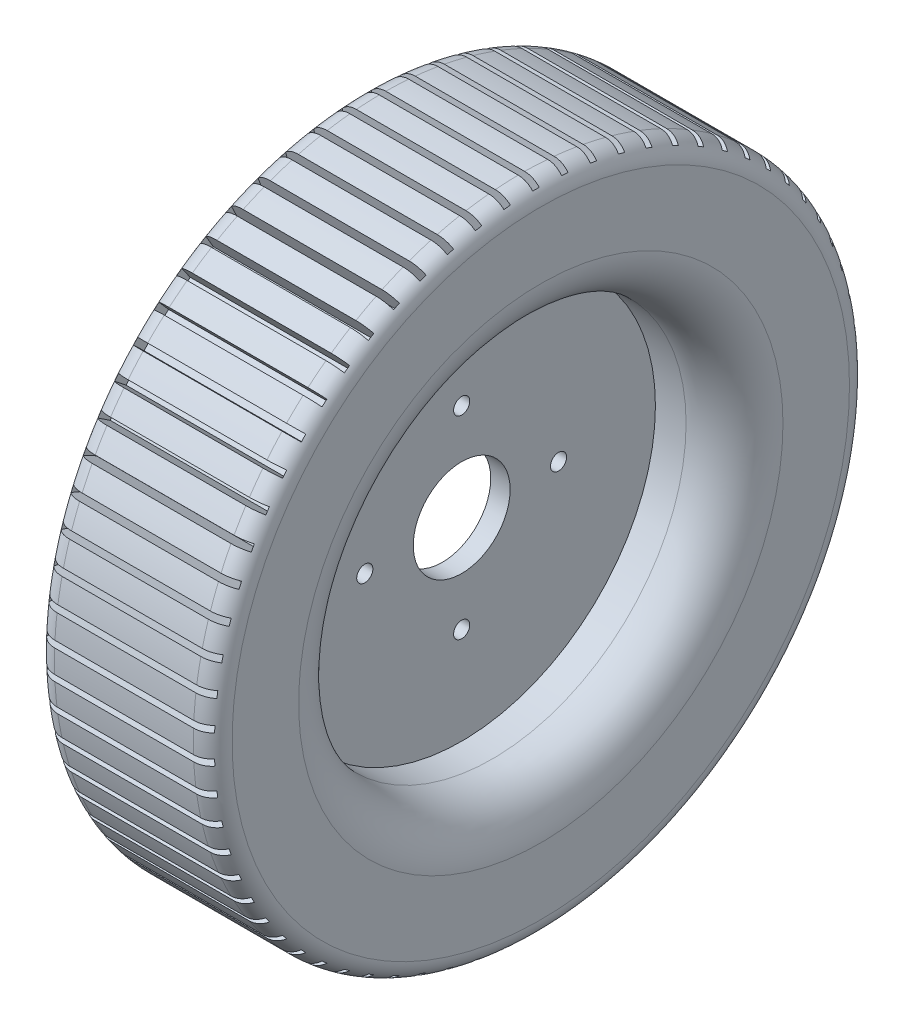
SolidWorks part; units mm, degrees
material "Rubber"
ref_plane "Front Plane" through (0, 0, 0) normal (0, 0, 1) x (1, 0, 0)
ref_plane "Top Plane" through (0, 0, 0) normal (0, 1, 0) x (1, 0, 0)
ref_plane "Right Plane" through (0, 0, 0) normal (1, 0, 0) x (0, 0, -1)
sketch "Sketch1" plane through (0, 0, 0) normal (1, 0, 0) x (0, 0, -1)
  circle A0 centre (0, 0) radius 101.6
  dimension "D1" = 203.2
extrude "Boss-Extrude1" add sketch "Sketch1" along normal mid plane 55
sketch "Sketch2" plane through (0, 0, 0) normal (1, 0, 0) x (0, 0, -1)
  circle A0 centre (0, 0) radius 60
  dimension "D1" = 120
extrude "Cut-Extrude1" cut sketch "Sketch2" against normal blind 500 from offset 3 offset against normal yes
extrude "Cut-Extrude2" cut sketch "Sketch2<2>" along normal blind 500 from offset 3
sketch "Sketch2<2>" plane through (0, 0, 0) normal (1, 0, 0) x (0, 0, -1) same geometry as "Sketch2"
fillet "Fillet1" radius 15 2 edges at (-27.5, 0, -60) (27.5, 0, -60)
fillet "Fillet5" radius 6 2 edges at (27.5, 0, -101.6) (-27.5, 0, -101.6)
sketch "Sketch5" plane through (0, 0, 0) normal (1, 0, 0) x (0, 0, -1)
  line L0 (8.4162, 104.6669) -> (10.4081, 104.4877)
  line L1 (-1, 105) -> (1, 105)
  line L2 (-1, 105) -> (-1, 95)
  line L3 (-1, 95) -> (1, 95)
  line L4 (1, 105) -> (1, 95)
  line L5 (-1, 105) -> (1, 95) construction
  line L6 (-1, 95) -> (1, 105) construction
  line L7 (10.4081, 104.4877) -> (9.5117, 94.5279)
  line L8 (8.4162, 104.6669) -> (7.5198, 94.7072)
  line L9 (7.5198, 94.7072) -> (9.5117, 94.5279)
  line L10 (17.7645, 103.4912) -> (19.7324, 103.134)
  line L11 (19.7324, 103.134) -> (17.9468, 93.2948)
  line L12 (17.7645, 103.4912) -> (15.979, 93.6519)
  line L13 (15.979, 93.6519) -> (17.9468, 93.2948)
  line L14 (26.9699, 101.4821) -> (28.8978, 100.9501)
  line L15 (28.8978, 100.9501) -> (26.2375, 91.3104)
  line L16 (26.9699, 101.4821) -> (24.3095, 91.8425)
  line L17 (24.3095, 91.8425) -> (26.2375, 91.3104)
  line L18 (35.9581, 98.656) -> (37.8306, 97.9533)
  line L19 (37.8306, 97.9533) -> (34.3168, 88.5909)
  line L20 (35.9581, 98.656) -> (32.4444, 89.2937)
  line L21 (32.4444, 89.2937) -> (34.3168, 88.5909)
  line L22 (44.6568, 95.0356) -> (46.4588, 94.1678)
  line L23 (46.4588, 94.1678) -> (42.1199, 85.1582)
  line L24 (44.6568, 95.0356) -> (40.318, 86.0259)
  line L25 (40.318, 86.0259) -> (42.1199, 85.1582)
  line L26 (52.996, 90.65) -> (54.7129, 89.6242)
  line L27 (54.7129, 89.6242) -> (49.5839, 81.0397)
  line L28 (52.996, 90.65) -> (47.867, 82.0655)
  line L29 (47.867, 82.0655) -> (49.5839, 81.0397)
  line L30 (60.9084, 85.5346) -> (62.5265, 84.359)
  line L31 (62.5265, 84.359) -> (56.6486, 76.2688)
  line L32 (60.9084, 85.5346) -> (55.0306, 77.4444)
  line L33 (55.0306, 77.4444) -> (56.6486, 76.2688)
  line L34 (68.3305, 79.7304) -> (69.8366, 78.4146)
  line L35 (69.8366, 78.4146) -> (63.2573, 70.8839)
  line L36 (68.3305, 79.7304) -> (61.7511, 72.1997)
  line L37 (61.7511, 72.1997) -> (63.2573, 70.8839)
  line L38 (75.2024, 73.2844) -> (76.5845, 71.8388)
  line L39 (76.5845, 71.8388) -> (69.3566, 64.9282)
  line L40 (75.2024, 73.2844) -> (67.9744, 66.3737)
  line L41 (67.9744, 66.3737) -> (69.3566, 64.9282)
  line L42 (81.4688, 66.2483) -> (82.7158, 64.6846)
  line L43 (82.7158, 64.6846) -> (74.8975, 58.4497)
  line L44 (81.4688, 66.2483) -> (73.6505, 60.0134)
  line L45 (73.6505, 60.0134) -> (74.8975, 58.4497)
  line L46 (87.0793, 58.6788) -> (88.1811, 57.0096)
  line L47 (88.1811, 57.0096) -> (79.8354, 51.5006)
  line L48 (87.0793, 58.6788) -> (78.7336, 53.1698)
  line L49 (78.7336, 53.1698) -> (79.8354, 51.5006)
  line L50 (91.9887, 50.6368) -> (92.9364, 48.8756)
  line L51 (92.9364, 48.8756) -> (84.1304, 44.1369)
  line L52 (91.9887, 50.6368) -> (83.1827, 45.8981)
  line L53 (83.1827, 45.8981) -> (84.1304, 44.1369)
  line L54 (96.1574, 42.1872) -> (96.9434, 40.3481)
  line L55 (96.9434, 40.3481) -> (87.7482, 36.4179)
  line L56 (96.1574, 42.1872) -> (86.9621, 38.2569)
  line L57 (86.9621, 38.2569) -> (87.7482, 36.4179)
  line L58 (99.5519, 33.3978) -> (100.17, 31.4957)
  line L59 (100.17, 31.4957) -> (90.6594, 28.4056)
  line L60 (99.5519, 33.3978) -> (90.0414, 30.3077)
  line L61 (90.0414, 30.3077) -> (90.6594, 28.4056)
  line L62 (102.1449, 24.3396) -> (102.59, 22.3898)
  line L63 (102.59, 22.3898) -> (92.8407, 20.1646)
  line L64 (102.1449, 24.3396) -> (92.3956, 22.1144)
  line L65 (92.3956, 22.1144) -> (92.8407, 20.1646)
  line L66 (103.9155, 15.0854) -> (104.184, 13.1035)
  line L67 (104.184, 13.1035) -> (94.2745, 11.7612)
  line L68 (103.9155, 15.0854) -> (94.006, 13.7431)
  line L69 (94.006, 13.7431) -> (94.2745, 11.7612)
  line L70 (104.8494, 5.7098) -> (104.9391, 3.7118)
  line L71 (104.9391, 3.7118) -> (94.9492, 3.2632)
  line L72 (104.8494, 5.7098) -> (94.8595, 5.2612)
  line L73 (94.8595, 5.2612) -> (94.9492, 3.2632)
  line L74 (104.9391, -3.7118) -> (104.8494, -5.7098)
  line L75 (104.8494, -5.7098) -> (94.8595, -5.2612)
  line L76 (104.9391, -3.7118) -> (94.9492, -3.2632)
  line L77 (94.9492, -3.2632) -> (94.8595, -5.2612)
  line L78 (104.184, -13.1035) -> (103.9155, -15.0854)
  line L79 (103.9155, -15.0854) -> (94.006, -13.7431)
  line L80 (104.184, -13.1035) -> (94.2745, -11.7612)
  line L81 (94.2745, -11.7612) -> (94.006, -13.7431)
  line L82 (102.59, -22.3898) -> (102.1449, -24.3396)
  line L83 (102.1449, -24.3396) -> (92.3956, -22.1144)
  line L84 (102.59, -22.3898) -> (92.8407, -20.1646)
  line L85 (92.8407, -20.1646) -> (92.3956, -22.1144)
  line L86 (100.17, -31.4957) -> (99.5519, -33.3978)
  line L87 (99.5519, -33.3978) -> (90.0414, -30.3077)
  line L88 (100.17, -31.4957) -> (90.6594, -28.4056)
  line L89 (90.6594, -28.4056) -> (90.0414, -30.3077)
  line L90 (96.9434, -40.3481) -> (96.1574, -42.1872)
  line L91 (96.1574, -42.1872) -> (86.9621, -38.2569)
  line L92 (96.9434, -40.3481) -> (87.7482, -36.4179)
  line L93 (87.7482, -36.4179) -> (86.9621, -38.2569)
  line L94 (92.9364, -48.8756) -> (91.9887, -50.6368)
  line L95 (91.9887, -50.6368) -> (83.1827, -45.8981)
  line L96 (92.9364, -48.8756) -> (84.1304, -44.1369)
  line L97 (84.1304, -44.1369) -> (83.1827, -45.8981)
  line L98 (88.1811, -57.0096) -> (87.0793, -58.6788)
  line L99 (87.0793, -58.6788) -> (78.7336, -53.1698)
  line L100 (88.1811, -57.0096) -> (79.8354, -51.5006)
  line L101 (79.8354, -51.5006) -> (78.7336, -53.1698)
  line L102 (82.7158, -64.6846) -> (81.4688, -66.2483)
  line L103 (81.4688, -66.2483) -> (73.6505, -60.0134)
  line L104 (82.7158, -64.6846) -> (74.8975, -58.4497)
  line L105 (74.8975, -58.4497) -> (73.6505, -60.0134)
  line L106 (76.5845, -71.8388) -> (75.2024, -73.2844)
  line L107 (75.2024, -73.2844) -> (67.9744, -66.3737)
  line L108 (76.5845, -71.8388) -> (69.3566, -64.9282)
  line L109 (69.3566, -64.9282) -> (67.9744, -66.3737)
  line L110 (69.8366, -78.4146) -> (68.3305, -79.7304)
  line L111 (68.3305, -79.7304) -> (61.7511, -72.1997)
  line L112 (69.8366, -78.4146) -> (63.2573, -70.8839)
  line L113 (63.2573, -70.8839) -> (61.7511, -72.1997)
  line L114 (62.5265, -84.359) -> (60.9084, -85.5346)
  line L115 (60.9084, -85.5346) -> (55.0306, -77.4444)
  line L116 (62.5265, -84.359) -> (56.6486, -76.2688)
  line L117 (56.6486, -76.2688) -> (55.0306, -77.4444)
  line L118 (54.7129, -89.6242) -> (52.996, -90.65)
  line L119 (52.996, -90.65) -> (47.867, -82.0655)
  line L120 (54.7129, -89.6242) -> (49.5839, -81.0397)
  line L121 (49.5839, -81.0397) -> (47.867, -82.0655)
  line L122 (46.4588, -94.1678) -> (44.6568, -95.0356)
  line L123 (44.6568, -95.0356) -> (40.318, -86.0259)
  line L124 (46.4588, -94.1678) -> (42.1199, -85.1582)
  line L125 (42.1199, -85.1582) -> (40.318, -86.0259)
  line L126 (37.8306, -97.9533) -> (35.9581, -98.656)
  line L127 (35.9581, -98.656) -> (32.4444, -89.2937)
  line L128 (37.8306, -97.9533) -> (34.3168, -88.5909)
  line L129 (34.3168, -88.5909) -> (32.4444, -89.2937)
  line L130 (28.8978, -100.9501) -> (26.9699, -101.4821)
  line L131 (26.9699, -101.4821) -> (24.3095, -91.8425)
  line L132 (28.8978, -100.9501) -> (26.2375, -91.3104)
  line L133 (26.2375, -91.3104) -> (24.3095, -91.8425)
  line L134 (19.7324, -103.134) -> (17.7645, -103.4912)
  line L135 (17.7645, -103.4912) -> (15.979, -93.6519)
  line L136 (19.7324, -103.134) -> (17.9468, -93.2948)
  line L137 (17.9468, -93.2948) -> (15.979, -93.6519)
  line L138 (10.4081, -104.4877) -> (8.4162, -104.6669)
  line L139 (8.4162, -104.6669) -> (7.5198, -94.7072)
  line L140 (10.4081, -104.4877) -> (9.5117, -94.5279)
  line L141 (9.5117, -94.5279) -> (7.5198, -94.7072)
  line L142 (1, -105) -> (-1, -105)
  line L143 (-1, -105) -> (-1, -95)
  line L144 (1, -105) -> (1, -95)
  line L145 (1, -95) -> (-1, -95)
  line L146 (-8.4162, -104.6669) -> (-10.4081, -104.4877)
  line L147 (-10.4081, -104.4877) -> (-9.5117, -94.5279)
  line L148 (-8.4162, -104.6669) -> (-7.5198, -94.7072)
  line L149 (-7.5198, -94.7072) -> (-9.5117, -94.5279)
  line L150 (-17.7645, -103.4912) -> (-19.7324, -103.134)
  line L151 (-19.7324, -103.134) -> (-17.9468, -93.2948)
  line L152 (-17.7645, -103.4912) -> (-15.979, -93.6519)
  line L153 (-15.979, -93.6519) -> (-17.9468, -93.2948)
  line L154 (-26.9699, -101.4821) -> (-28.8978, -100.9501)
  line L155 (-28.8978, -100.9501) -> (-26.2375, -91.3104)
  line L156 (-26.9699, -101.4821) -> (-24.3095, -91.8425)
  line L157 (-24.3095, -91.8425) -> (-26.2375, -91.3104)
  line L158 (-35.9581, -98.656) -> (-37.8306, -97.9533)
  line L159 (-37.8306, -97.9533) -> (-34.3168, -88.5909)
  line L160 (-35.9581, -98.656) -> (-32.4444, -89.2937)
  line L161 (-32.4444, -89.2937) -> (-34.3168, -88.5909)
  line L162 (-44.6568, -95.0356) -> (-46.4588, -94.1678)
  line L163 (-46.4588, -94.1678) -> (-42.1199, -85.1582)
  line L164 (-44.6568, -95.0356) -> (-40.318, -86.0259)
  line L165 (-40.318, -86.0259) -> (-42.1199, -85.1582)
  line L166 (-52.996, -90.65) -> (-54.7129, -89.6242)
  line L167 (-54.7129, -89.6242) -> (-49.5839, -81.0397)
  line L168 (-52.996, -90.65) -> (-47.867, -82.0655)
  line L169 (-47.867, -82.0655) -> (-49.5839, -81.0397)
  line L170 (-60.9084, -85.5346) -> (-62.5265, -84.359)
  line L171 (-62.5265, -84.359) -> (-56.6486, -76.2688)
  line L172 (-60.9084, -85.5346) -> (-55.0306, -77.4444)
  line L173 (-55.0306, -77.4444) -> (-56.6486, -76.2688)
  line L174 (-68.3305, -79.7304) -> (-69.8366, -78.4146)
  line L175 (-69.8366, -78.4146) -> (-63.2573, -70.8839)
  line L176 (-68.3305, -79.7304) -> (-61.7511, -72.1997)
  line L177 (-61.7511, -72.1997) -> (-63.2573, -70.8839)
  line L178 (-75.2024, -73.2844) -> (-76.5845, -71.8388)
  line L179 (-76.5845, -71.8388) -> (-69.3566, -64.9282)
  line L180 (-75.2024, -73.2844) -> (-67.9744, -66.3737)
  line L181 (-67.9744, -66.3737) -> (-69.3566, -64.9282)
  line L182 (-81.4688, -66.2483) -> (-82.7158, -64.6846)
  line L183 (-82.7158, -64.6846) -> (-74.8975, -58.4497)
  line L184 (-81.4688, -66.2483) -> (-73.6505, -60.0134)
  line L185 (-73.6505, -60.0134) -> (-74.8975, -58.4497)
  line L186 (-87.0793, -58.6788) -> (-88.1811, -57.0096)
  line L187 (-88.1811, -57.0096) -> (-79.8354, -51.5006)
  line L188 (-87.0793, -58.6788) -> (-78.7336, -53.1698)
  line L189 (-78.7336, -53.1698) -> (-79.8354, -51.5006)
  line L190 (-91.9887, -50.6368) -> (-92.9364, -48.8756)
  line L191 (-92.9364, -48.8756) -> (-84.1304, -44.1369)
  line L192 (-91.9887, -50.6368) -> (-83.1827, -45.8981)
  line L193 (-83.1827, -45.8981) -> (-84.1304, -44.1369)
  line L194 (-96.1574, -42.1872) -> (-96.9434, -40.3481)
  line L195 (-96.9434, -40.3481) -> (-87.7482, -36.4179)
  line L196 (-96.1574, -42.1872) -> (-86.9621, -38.2569)
  line L197 (-86.9621, -38.2569) -> (-87.7482, -36.4179)
  line L198 (-99.5519, -33.3978) -> (-100.17, -31.4957)
  line L199 (-100.17, -31.4957) -> (-90.6594, -28.4056)
  line L200 (-99.5519, -33.3978) -> (-90.0414, -30.3077)
  line L201 (-90.0414, -30.3077) -> (-90.6594, -28.4056)
  line L202 (-102.1449, -24.3396) -> (-102.59, -22.3898)
  line L203 (-102.59, -22.3898) -> (-92.8407, -20.1646)
  line L204 (-102.1449, -24.3396) -> (-92.3956, -22.1144)
  line L205 (-92.3956, -22.1144) -> (-92.8407, -20.1646)
  line L206 (-103.9155, -15.0854) -> (-104.184, -13.1035)
  line L207 (-104.184, -13.1035) -> (-94.2745, -11.7612)
  line L208 (-103.9155, -15.0854) -> (-94.006, -13.7431)
  line L209 (-94.006, -13.7431) -> (-94.2745, -11.7612)
  line L210 (-104.8494, -5.7098) -> (-104.9391, -3.7118)
  line L211 (-104.9391, -3.7118) -> (-94.9492, -3.2632)
  line L212 (-104.8494, -5.7098) -> (-94.8595, -5.2612)
  line L213 (-94.8595, -5.2612) -> (-94.9492, -3.2632)
  line L214 (-104.9391, 3.7118) -> (-104.8494, 5.7098)
  line L215 (-104.8494, 5.7098) -> (-94.8595, 5.2612)
  line L216 (-104.9391, 3.7118) -> (-94.9492, 3.2632)
  line L217 (-94.9492, 3.2632) -> (-94.8595, 5.2612)
  line L218 (-104.184, 13.1035) -> (-103.9155, 15.0854)
  line L219 (-103.9155, 15.0854) -> (-94.006, 13.7431)
  line L220 (-104.184, 13.1035) -> (-94.2745, 11.7612)
  line L221 (-94.2745, 11.7612) -> (-94.006, 13.7431)
  line L222 (-102.59, 22.3898) -> (-102.1449, 24.3396)
  line L223 (-102.1449, 24.3396) -> (-92.3956, 22.1144)
  line L224 (-102.59, 22.3898) -> (-92.8407, 20.1646)
  line L225 (-92.8407, 20.1646) -> (-92.3956, 22.1144)
  line L226 (-100.17, 31.4957) -> (-99.5519, 33.3978)
  line L227 (-99.5519, 33.3978) -> (-90.0414, 30.3077)
  line L228 (-100.17, 31.4957) -> (-90.6594, 28.4056)
  line L229 (-90.6594, 28.4056) -> (-90.0414, 30.3077)
  line L230 (-96.9434, 40.3481) -> (-96.1574, 42.1872)
  line L231 (-96.1574, 42.1872) -> (-86.9621, 38.2569)
  line L232 (-96.9434, 40.3481) -> (-87.7482, 36.4179)
  line L233 (-87.7482, 36.4179) -> (-86.9621, 38.2569)
  line L234 (-92.9364, 48.8756) -> (-91.9887, 50.6368)
  line L235 (-91.9887, 50.6368) -> (-83.1827, 45.8981)
  line L236 (-92.9364, 48.8756) -> (-84.1304, 44.1369)
  line L237 (-84.1304, 44.1369) -> (-83.1827, 45.8981)
  line L238 (-88.1811, 57.0096) -> (-87.0793, 58.6788)
  line L239 (-87.0793, 58.6788) -> (-78.7336, 53.1698)
  line L240 (-88.1811, 57.0096) -> (-79.8354, 51.5006)
  line L241 (-79.8354, 51.5006) -> (-78.7336, 53.1698)
  line L242 (-82.7158, 64.6846) -> (-81.4688, 66.2483)
  line L243 (-81.4688, 66.2483) -> (-73.6505, 60.0134)
  line L244 (-82.7158, 64.6846) -> (-74.8975, 58.4497)
  line L245 (-74.8975, 58.4497) -> (-73.6505, 60.0134)
  line L246 (-76.5845, 71.8388) -> (-75.2024, 73.2844)
  line L247 (-75.2024, 73.2844) -> (-67.9744, 66.3737)
  line L248 (-76.5845, 71.8388) -> (-69.3566, 64.9282)
  line L249 (-69.3566, 64.9282) -> (-67.9744, 66.3737)
  line L250 (-69.8366, 78.4146) -> (-68.3305, 79.7304)
  line L251 (-68.3305, 79.7304) -> (-61.7511, 72.1997)
  line L252 (-69.8366, 78.4146) -> (-63.2573, 70.8839)
  line L253 (-63.2573, 70.8839) -> (-61.7511, 72.1997)
  line L254 (-62.5265, 84.359) -> (-60.9084, 85.5346)
  line L255 (-60.9084, 85.5346) -> (-55.0306, 77.4444)
  line L256 (-62.5265, 84.359) -> (-56.6486, 76.2688)
  line L257 (-56.6486, 76.2688) -> (-55.0306, 77.4444)
  line L258 (-54.7129, 89.6242) -> (-52.996, 90.65)
  line L259 (-52.996, 90.65) -> (-47.867, 82.0655)
  line L260 (-54.7129, 89.6242) -> (-49.5839, 81.0397)
  line L261 (-49.5839, 81.0397) -> (-47.867, 82.0655)
  line L262 (-46.4588, 94.1678) -> (-44.6568, 95.0356)
  line L263 (-44.6568, 95.0356) -> (-40.318, 86.0259)
  line L264 (-46.4588, 94.1678) -> (-42.1199, 85.1582)
  line L265 (-42.1199, 85.1582) -> (-40.318, 86.0259)
  line L266 (-37.8306, 97.9533) -> (-35.9581, 98.656)
  line L267 (-35.9581, 98.656) -> (-32.4444, 89.2937)
  line L268 (-37.8306, 97.9533) -> (-34.3168, 88.5909)
  line L269 (-34.3168, 88.5909) -> (-32.4444, 89.2937)
  line L270 (-28.8978, 100.9501) -> (-26.9699, 101.4821)
  line L271 (-26.9699, 101.4821) -> (-24.3095, 91.8425)
  line L272 (-28.8978, 100.9501) -> (-26.2375, 91.3104)
  line L273 (-26.2375, 91.3104) -> (-24.3095, 91.8425)
  line L274 (-19.7324, 103.134) -> (-17.7645, 103.4912)
  line L275 (-17.7645, 103.4912) -> (-15.979, 93.6519)
  line L276 (-19.7324, 103.134) -> (-17.9468, 93.2948)
  line L277 (-17.9468, 93.2948) -> (-15.979, 93.6519)
  line L278 (-10.4081, 104.4877) -> (-8.4162, 104.6669)
  line L279 (-8.4162, 104.6669) -> (-7.5198, 94.7072)
  line L280 (-10.4081, 104.4877) -> (-9.5117, 94.5279)
  line L281 (-9.5117, 94.5279) -> (-7.5198, 94.7072)
  circle A0 centre (0, 0) radius 100
  point P3 (0, 100)
  point P10 (0, 95)
  point P286 (0, 0)
  point P287 (-8.5157, 94.6176)
  dimension "D1" = 200
  dimension "D2" = 2
  dimension "D3" = 10
  dimension "D5" = 8.5157
  dimension "D4" = 70
sketch "Sketch6" plane through (3, 0, 0) normal (1, 0, 0) x (0, 0, -1)
  circle A0 centre (0, 0) radius 15
  dimension "D1" = 30
extrude "Cut-Extrude4" cut sketch "Sketch5" against normal mid plane 52 contours L15 L17 L16 L14 | L11 L13 L12 L10 | L7 L9 L8 L0 | L4 L3 L2 L1 | L279 L281 L280 L278 | L275 L277 L276 L274 | L19 L21 L20 L18 | L24 L25 L23 L22 | L27 L29 L28 L26 | L32 L33 L31 L30 | L36 L37 L35 L34 | L40 L41 L39 L38 | L44 L45 L43 L42 | L46 L47 L49 L48 | L52 L53 L51 L50 | L56 L57 L55 L54 | L60 L61 L59 L58 | L63 L65 L64 L62 | L68 L69 L67 L66 | L72 L73 L71 L70 | L75 L77 L76 L74 | L79 L81 L80 L78 | L271 L273 L272 L270 | L267 L269 L268 L266 | L263 L265 L264 L262 | L259 L261 L260 L258 | L256 L257 L255 L254 | L251 L253 L252 L250 | L247 L249 L248 L246 | L243 L245 L244 L242 | L238 L239 L241 L240 | L235 L237 L236 L234 | L231 L233 L232 L230 | L227 L229 L228 L226 | L223 L225 L224 L222 | L219 L221 L220 L218 | L216 L217 L215 L214 | L211 L213 L212 L210 | L207 L209 L208 L206 | L203 L205 L204 L202 | L199 L201 L200 L198 | L195 L197 L196 L194 | L191 L193 L192 L190 | L83 L85 L84 L82 | L87 L89 L88 L86 | L91 L93 L92 L90 | L95 L97 L96 L94 | L99 L101 L100 L98 | L103 L105 L104 L102 | L106 L107 L109 L108 | L112 L113 L111 L110 | L115 L117 L116 L114 | L119 L121 L120 L118 | L123 L125 L124 L122 | L127 L129 L128 L126 | L131 L133 L132 L130 | L135 L137 L136 L134 | L139 L141 L140 L138 | L143 L145 L144 L142 | L147 L149 L148 L146 | L151 L153 L152 L150 | L155 L157 L156 L154 | L159 L161 L160 L158 | L163 L165 L164 L162 | L167 L169 L168 L166 | L171 L173 L172 L170 | L175 L177 L176 L174 | L179 L181 L180 L178 | L183 L185 L184 L182 | L187 L189 L188 L186
extrude "Cut-Extrude5" cut sketch "Sketch6" against normal mid plane 48
sketch "Sketch7" plane through (-3, 0, 0) normal (-1, 0, 0) x (0, 0, 1)
  circle A0 centre (30, 0) radius 2.5
  circle A1 centre (0, -30) radius 2.5
  circle A2 centre (-30, 0) radius 2.5
  circle A3 centre (0, 30) radius 2.5
  point P12 (0, 0)
  dimension "D1" = 5
  dimension "D2" = 30
  dimension "D4" = 30
  dimension "D3" = 4
extrude "Cut-Extrude6" cut sketch "Sketch7" against normal mid plane 48
